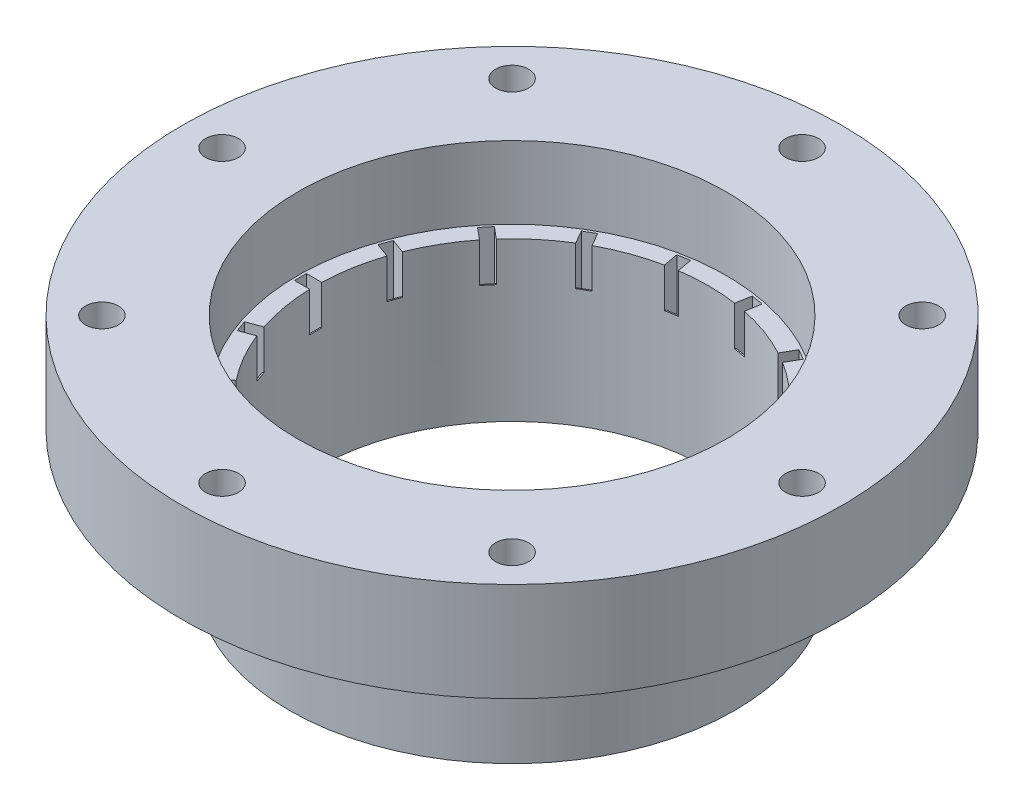
SolidWorks part; units mm, degrees
ref_plane "Front Plane" through (0, 0, 0) normal (0, 0, 1) x (1, 0, 0)
ref_plane "Top Plane" through (0, 0, 0) normal (0, 1, 0) x (1, 0, 0)
ref_plane "Right Plane" through (0, 0, 0) normal (1, 0, 0) x (0, 0, -1)
sketch "Sketch1" plane through (0, 0, 0) normal (0, 1, 0) x (1, 0, 0)
  circle A0 centre (0, 0) radius 37.846
  circle A1 centre (0, 0) radius 42.926
  circle A2 centre (0, 0) radius 63.5
  dimension "D1" = 75.692
  dimension "D2" = 85.852
  dimension "D3" = 127
extrude "Boss-Extrude1" add sketch "Sketch1" along normal blind 19.05 contours A2 A1 | A1 A0 region at (-41.7119, 0, 0) region at (-61.7039, 0, 0)
sketch "Sketch2" plane through (0, 19.05, 0) normal (0, 1, 0) x (1, 0, 0)
  line L0 (0, 0) -> (0, 85.704) construction
  circle A0 centre (0, 55.88) radius 3.175
  circle A1 centre (0, 0) radius 63.5 construction
  dimension "D1" = 6.35
  dimension "D2" = 55.88
extrude "Cut-Extrude1" cut sketch "Sketch2" against normal through all
ref_axis "Axis1" through (0, 19.05, 0) along (0, -1, 0)
pattern_circular "CirPattern1" count 8 every 45 about axis through (0, 19.05, 0) along (0, -1, 0) of "Cut-Extrude1"
extrude "Boss-Extrude2" add sketch "Sketch1<3>" against normal blind 25.4 contours A1 A0 region at (-41.7119, 0, 0)
sketch "Sketch1<3>" plane through (0, 0, 0) normal (0, 1, 0) x (1, 0, 0) same geometry as "Sketch1"
sketch "Sketch3" plane through (0, 19.05, 0) normal (0, 1, 0) x (1, 0, 0)
  circle A0 centre (0, 0) radius 37.846
  circle A1 centre (0, 0) radius 41.275
  dimension "D1" = 82.55
extrude "Cut-Extrude2" cut sketch "Sketch3" against normal blind 13.97
sketch "Sketch4" plane through (0, -25.4, 0) normal (0, -1, 0) x (1, 0, 0)
  line L0 (0, 0) -> (-69.031, 0) construction
  line L2 (-40.7714, -1.1542) -> (-38.074, -1.1542)
  line L3 (-40.7714, -1.1542) -> (-40.7714, 1.1542)
  line L4 (-40.7714, 1.1542) -> (-38.074, 1.1542)
  line L5 (-38.074, -1.1542) -> (-38.074, 1.1542)
  line L6 (-40.7714, -1.1542) -> (-38.074, 1.1542) construction
  line L7 (-40.7714, 1.1542) -> (-38.074, -1.1542) construction
  point P3 (-39.4227, 0)
  point P8 (-39.6872, 0)
extrude "Cut-Extrude3" cut sketch "Sketch4" against normal through all
sketch "Sketch5" plane through (-38.074, 0, 0) normal (-1, 0, 0) x (0, 0, 1)
  line L0 (1.1542, 5.08) -> (1.1542, -25.4) construction
  line L1 (-1.1542, 5.08) -> (1.1542, 5.08)
  line L2 (-1.1542, 5.08) -> (-1.1542, -2.54)
  line L3 (-1.1542, -2.54) -> (1.1542, -2.54)
  line L4 (1.1542, 5.08) -> (1.1542, -2.54)
  dimension "D1" = 7.62
extrude "Cut-Extrude4" cut sketch "Sketch5" against normal blind 2.54
pattern_circular "CirPattern2" count 18 every 20 about axis through (0, 19.05, 0) along (0, -1, 0) of "Cut-Extrude4", "Cut-Extrude3"
